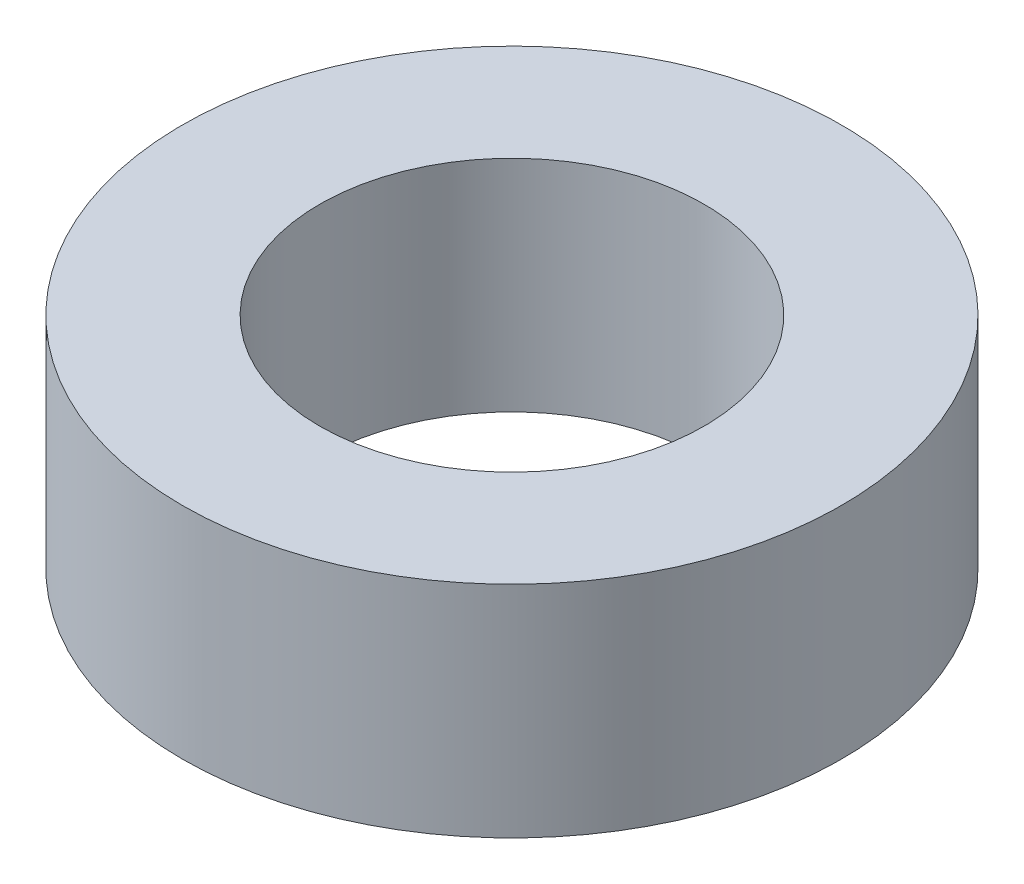
SolidWorks part; units mm, degrees
ref_plane "Front Plane" through (0, 0, 0) normal (0, 0, 1) x (1, 0, 0)
ref_plane "Top Plane" through (0, 0, 0) normal (0, 1, 0) x (1, 0, 0)
ref_plane "Right Plane" through (0, 0, 0) normal (1, 0, 0) x (0, 0, -1)
sketch "Sketch1" plane through (0, 0, 0) normal (0, 1, 0) x (1, 0, 0)
  circle A0 centre (0, 0) radius 30
  dimension "FLANGE_OD" = 60
extrude "Boss-Extrude1" add sketch "Sketch1" along normal blind 20
sketch "Sketch2" plane through (0, 0, 0) normal (0, 1, 0) x (1, 0, 0)
  circle A0 centre (0, 0) radius 17.5
  dimension "BORE_D" = 35
extrude "Cut-Extrude1" cut sketch "Sketch2" along normal through all
sketch "Sketch3" plane through (0, 20, 0) normal (0, 1, 0) x (1, 0, 0)
  circle A0 centre (0, 0) radius 11.9156 construction
  circle A1 centre (-11.9156, 0) radius 1.8034
  dimension "BOLT_D" = 3.6067
  dimension "BOLT_PCD" = 23.8312
extrude "Cut-Extrude2" cut sketch "Sketch3" against normal blind 17.1642 rebuild error yes
pattern_circular "CirPattern1" count 3 over 360 rebuild error yes
